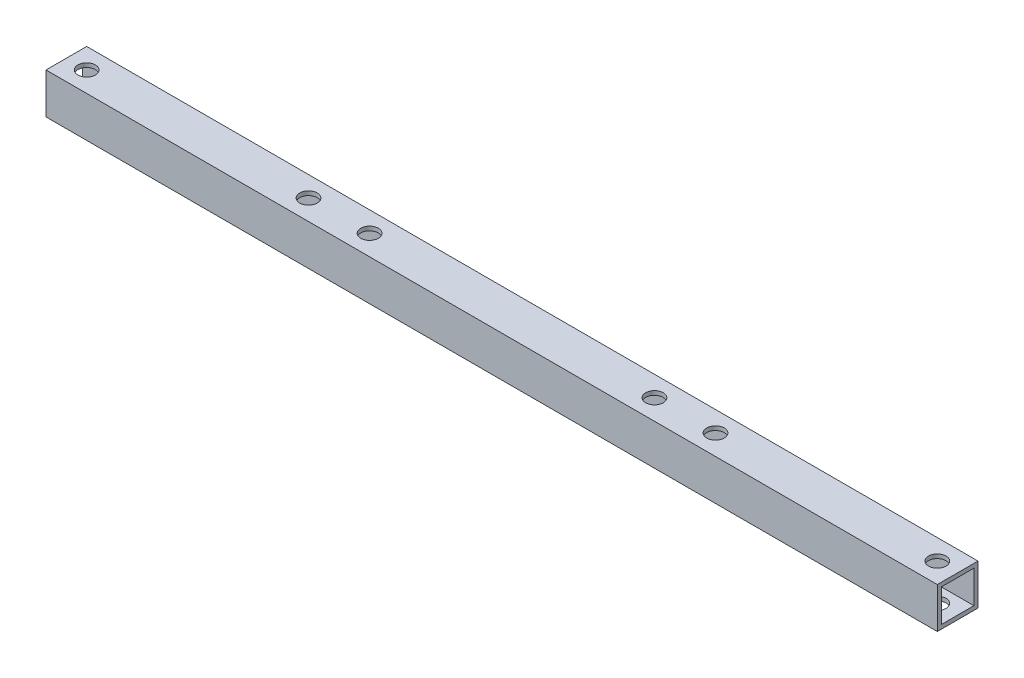
SolidWorks part; units mm, degrees
material "5052-H34"
ref_plane "正面" through (0, 0, 0) normal (0, 0, 1) x (1, 0, 0)
ref_plane "平面" through (0, 0, 0) normal (0, 1, 0) x (1, 0, 0)
ref_plane "右側面" through (0, 0, 0) normal (1, 0, 0) x (0, 0, -1)
sketch "ｽｹｯﾁ1" plane through (0, 0, 0) normal (1, 0, 0) x (0, 0, -1)
  line L1 (-5, 5) -> (5, 5)
  line L2 (-5, 5) -> (-5, -5)
  line L3 (-5, -5) -> (5, -5)
  line L4 (5, 5) -> (5, -5)
  line L5 (-5, 5) -> (5, -5) construction
  line L6 (-5, -5) -> (5, 5) construction
  point P0 (0, 0)
  dimension "D1" = 10
  dimension "D2" = 10
extrude "押し出し-薄板1" add sketch "ｽｹｯﾁ1" along normal blind 219 thin thin type one direction reverse wall 1
sketch "ｽｹｯﾁ2" plane through (0, 5, 0) normal (0, 1, 0) x (1, 0, 0)
  line L0 (109.5, 5) -> (109.5, -5) construction
  line L1 (219, 5) -> (0, 5) construction
  line L2 (219, -5) -> (0, -5) construction
  line L3 (0, 0) -> (5, 0) construction
  line L4 (109.5, 0) -> (159.5, 0) construction
  circle A0 centre (5, 0) radius 2.15
  circle A1 centre (214, 0) radius 2.15
  circle A2 centre (159.5, 0) radius 2.15
  circle A3 centre (59.5, 0) radius 2.15
  circle A4 centre (144.5, 0) radius 2.15
  circle A5 centre (74.5, 0) radius 2.15
  dimension "D2" = 4.3
  dimension "D3" = 4.3
  dimension "D5" = 4.3
  dimension "D1" = 5
  dimension "D4" = 100
  dimension "D6" = 70
extrude "ｶｯﾄ - 押し出し1" cut sketch "ｽｹｯﾁ2" against normal through all
